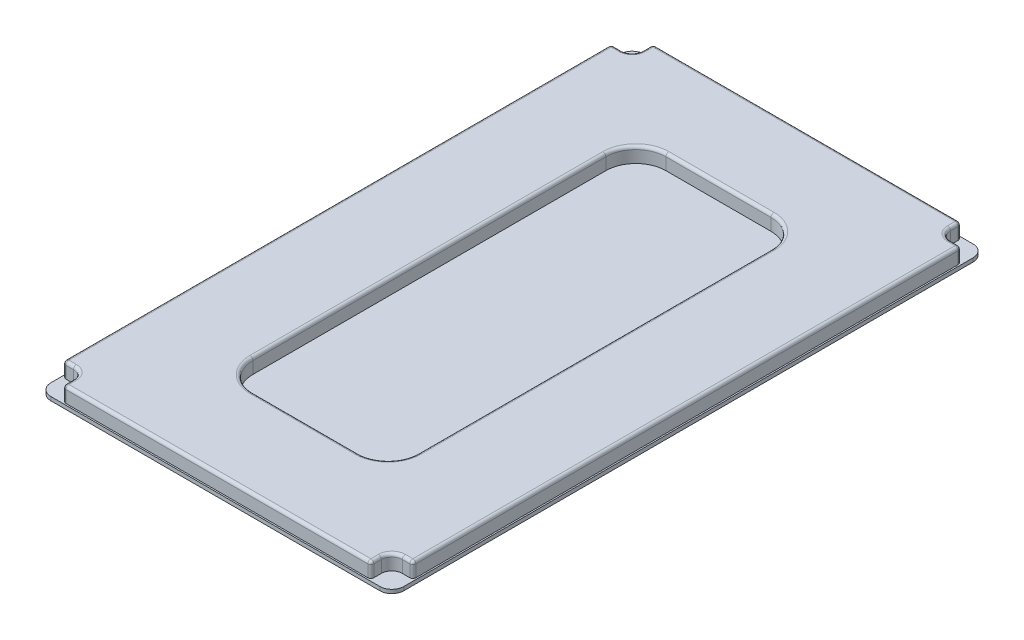
SolidWorks part; units mm, degrees
ref_plane "Front" through (0, 0, 0) normal (0, 0, 1) x (1, 0, 0)
ref_plane "Top" through (0, 0, 0) normal (0, 1, 0) x (1, 0, 0)
ref_plane "Right" through (0, 0, 0) normal (1, 0, 0) x (0, 0, -1)
sketch "Sketch1" plane through (0, 0, 0) normal (0, 1, 0) x (1, 0, 0)
  line L1 (2.54, 0) -> (72.0725, 0)
  line L2 (0, 2.54) -> (0, 122.8725)
  line L3 (2.54, 125.4125) -> (72.0725, 125.4125)
  line L4 (74.6125, 2.54) -> (74.6125, 122.8725)
  arc A0 (0, 122.8725) -> (2.54, 125.4125) centre (2.54, 122.8725) cw
  arc A1 (2.54, 0) -> (0, 2.54) centre (2.54, 2.54) cw
  arc A2 (72.0725, 0) -> (74.6125, 2.54) centre (72.0725, 2.54) ccw
  arc A3 (72.0725, 125.4125) -> (74.6125, 122.8725) centre (72.0725, 122.8725) cw
  point P8 (0, 0)
  point P11 (74.6125, 0)
  point P14 (74.6125, 125.4125)
  dimension "D3" = 2.54
  dimension "D1" = 74.6125
  dimension "D2" = 125.4125
sheet metal parameters "Sheet-Metal1" thickness 0.7937 parameters "D1"=0.7366
base flange "Base-Flange1" sketch "Sketch1" thickness 0.7937 reverse thickness direction yes parameters "D1"=0.7366
sketch "Sketch3" plane through (0, 0.7937, 0) normal (0, 1, 0) x (-1, 0, 0)
  line L0 (0, -62.7063) -> (-74.6125, -62.7063) construction
  line L1 (-37.3062, 0) -> (-37.3062, -125.4125) construction
  line L3 (-26.1938, -19.05) -> (-48.4187, -19.05)
  line L4 (0, -122.8725) -> (0, -2.54)
  line L5 (-2.54, 0) -> (-72.0725, 0)
  line L6 (-74.6125, -2.54) -> (-74.6125, -122.8725)
  line L7 (-72.0725, -125.4125) -> (-2.54, -125.4125)
  line L8 (0, -122.8725) -> (0, -2.54) construction
  line L9 (-2.54, 0) -> (-72.0725, 0) construction
  line L10 (-74.6125, -2.54) -> (-74.6125, -122.8725) construction
  line L11 (-72.0725, -125.4125) -> (-2.54, -125.4125) construction
  line L12 (-19.8438, -25.4) -> (-19.8438, -100.0125)
  line L13 (-26.1937, -106.3625) -> (-48.4187, -106.3625)
  line L14 (-54.7687, -25.4) -> (-54.7687, -100.0125)
  line L18 (-69.85, -125.095) -> (-4.7625, -125.095)
  line L19 (-74.295, -4.7625) -> (-74.295, -120.65)
  line L20 (-0.3175, -120.65) -> (-0.3175, -4.7625)
  line L21 (-4.7625, -0.3175) -> (-69.85, -0.3175)
  line L22 (-2.54, -120.65) -> (-0.3175, -120.65)
  line L23 (-4.7625, -122.8725) -> (-4.7625, -125.095)
  line L24 (-2.54, -4.7625) -> (-0.3175, -4.7625)
  line L25 (-4.7625, -2.54) -> (-4.7625, -0.3175)
  line L26 (-72.0725, -4.7625) -> (-74.295, -4.7625)
  line L27 (-69.85, -2.54) -> (-69.85, -0.3175)
  line L28 (-72.0725, -120.65) -> (-74.295, -120.65)
  line L29 (-69.85, -122.8725) -> (-69.85, -125.095)
  arc A0 (-19.8438, -100.0125) -> (-26.1937, -106.3625) centre (-26.1937, -100.0125) cw
  arc A1 (-26.1938, -19.05) -> (-19.8438, -25.4) centre (-26.1938, -25.4) cw
  arc A2 (-48.4187, -19.05) -> (-54.7687, -25.4) centre (-48.4187, -25.4) ccw
  arc A3 (-48.4187, -106.3625) -> (-54.7687, -100.0125) centre (-48.4187, -100.0125) cw
  arc A4 (-2.54, -125.4125) -> (0, -122.8725) centre (-2.54, -122.8725) ccw
  arc A5 (0, -2.54) -> (-2.54, 0) centre (-2.54, -2.54) ccw
  arc A6 (-72.0725, 0) -> (-74.6125, -2.54) centre (-72.0725, -2.54) ccw
  arc A7 (-74.6125, -122.8725) -> (-72.0725, -125.4125) centre (-72.0725, -122.8725) ccw
  arc A8 (-2.54, -125.4125) -> (0, -122.8725) centre (-2.54, -122.8725) ccw construction
  arc A9 (0, -2.54) -> (-2.54, 0) centre (-2.54, -2.54) ccw construction
  arc A10 (-72.0725, 0) -> (-74.6125, -2.54) centre (-72.0725, -2.54) ccw construction
  arc A11 (-74.6125, -122.8725) -> (-72.0725, -125.4125) centre (-72.0725, -122.8725) ccw construction
  arc A16 (-2.54, -120.65) -> (-4.7625, -122.8725) centre (-2.54, -122.8725) ccw
  arc A17 (-2.54, -4.7625) -> (-4.7625, -2.54) centre (-2.54, -2.54) cw
  arc A18 (-72.0725, -4.7625) -> (-69.85, -2.54) centre (-72.0725, -2.54) ccw
  arc A19 (-72.0725, -120.65) -> (-69.85, -122.8725) centre (-72.0725, -122.8725) cw
  point P20 (-37.3062, -106.3625)
  point P21 (-54.7687, -62.7063)
  point P26 (-19.8438, -19.05)
  point P29 (-54.7687, -19.05)
  point P32 (-54.7687, -106.3625)
  dimension "D4" = 6.35
  dimension "D5" = 6.35
  dimension "D7" = 2.2225
  dimension "D2" = 34.925
  dimension "D3" = 87.3125
  dimension "D1" = 0
  dimension "D6" = 0.3175
extrude "Extrude1" add sketch "Sketch3" along normal blind 3.175 separate body
fillet "Fillet1" radius 0.635 8 edges at (0.3175, 2.3813, -120.65) (4.7625, 2.3813, -125.095) (0.3175, 2.3813, -4.7625) (4.7625, 2.3813, -0.3175) (69.85, 2.3813, -0.3175) (74.295, 2.3813, -4.7625) (74.295, 2.3813, -120.65) (69.85, 2.3813, -125.095)
fillet "Fillet2" radius 0.635 32 edges at (21.7036, 3.9688, -20.9099) (37.3062, 3.9688, -19.05) (52.9089, 3.9688, -20.9099) (54.7687, 3.9688, -62.7063) (52.9089, 3.9688, -104.5026) (37.3062, 3.9688, -106.3625) (21.7036, 3.9688, -104.5026) (19.8438, 3.9688, -62.7063) (0.5035, 3.9688, -120.464) (1.7462, 3.9688, -120.65) (4.1115, 3.9688, -121.301) (4.7625, 3.9688, -123.6663) (4.9485, 3.9688, -124.909) (37.3062, 3.9688, -125.095) (69.664, 3.9688, -124.909) (69.85, 3.9688, -123.6663) (70.501, 3.9688, -121.301) (72.8662, 3.9688, -120.65) (74.109, 3.9688, -120.464) (74.295, 3.9688, -62.7063) (74.109, 3.9688, -4.9485) (72.8662, 3.9688, -4.7625) (70.501, 3.9688, -4.1115) (69.85, 3.9688, -1.7462) (69.664, 3.9688, -0.5035) (37.3062, 3.9688, -0.3175) (4.9485, 3.9688, -0.5035) (4.7625, 3.9688, -1.7462) (4.1115, 3.9688, -4.1115) (1.7462, 3.9688, -4.7625) (0.5035, 3.9688, -4.9485) (0.3175, 3.9688, -62.7063)
flat pattern "Flat-Pattern1" [suppressed]
sketch "Bend-Lines1" plane through (0, 0, 0) normal (0, 1, 0) x (-1, 0, 0)
